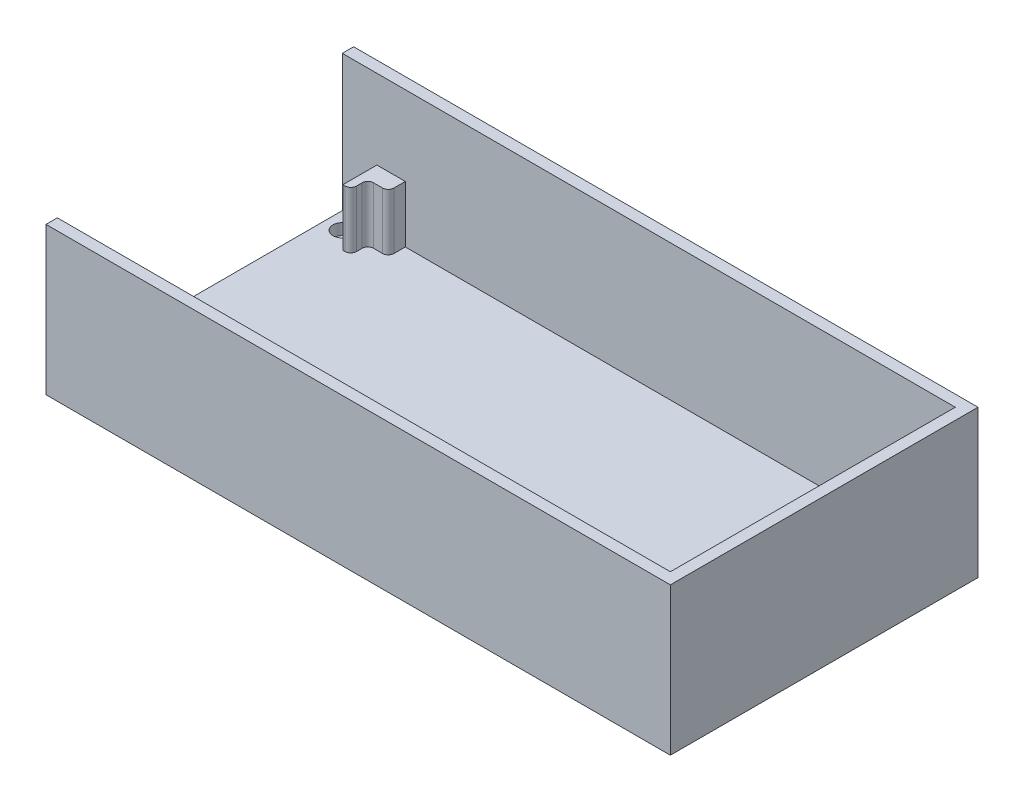
SolidWorks part; units mm, degrees
ref_plane "前视基准面" through (0, 0, 0) normal (0, 0, 1) x (1, 0, 0)
ref_plane "上视基准面" through (0, 0, 0) normal (0, 1, 0) x (1, 0, 0)
ref_plane "右视基准面" through (0, 0, 0) normal (1, 0, 0) x (0, 0, -1)
sketch "草图1" plane through (0, 0, 0) normal (0, 1, 0) x (1, 0, 0)
  line L0 (-56, -27.1) -> (-56, 27.1)
  line L1 (-54, -25.1) -> (54, -25.1)
  line L2 (-54, -25.1) -> (-54, 25.1)
  line L3 (-54, 25.1) -> (54, 25.1)
  line L4 (54, -25.1) -> (54, 25.1)
  line L5 (-54, -25.1) -> (54, 25.1) construction
  line L6 (-54, 25.1) -> (54, -25.1) construction
  line L7 (-56, 27.1) -> (56, 27.1)
  line L8 (56, -27.1) -> (56, 27.1)
  line L9 (-56, -27.1) -> (56, -27.1)
  point P0 (0, 0)
  dimension "D1" = 108
  dimension "D2" = 50.2
  dimension "D3" = 2
extrude "凸台-拉伸1" add sketch "草图1" along normal blind 26
sketch "草图2" plane through (0, 0, 0) normal (0, 1, 0) x (1, 0, 0)
  line L0 (-54, -25.1) -> (54, -25.1) construction
  line L1 (54, -25.1) -> (54, 25.1) construction
  line L2 (-54, 25.1) -> (-54, -25.1) construction
  line L3 (54, 25.1) -> (-54, 25.1) construction
  line L4 (-54, -25.1) -> (54, -25.1)
  line L5 (54, -25.1) -> (54, 25.1)
  line L6 (-54, 25.1) -> (-54, -25.1)
  line L7 (54, 25.1) -> (-54, 25.1)
  line L8 (0, 0) -> (-4.4301, 0) construction
  line L9 (0, 0) -> (0, -5.1784) construction
  circle A0 centre (-51, 22.1) radius 1.65
  circle A4 centre (51, 22.1) radius 1.65
  circle A5 centre (51, -22.1) radius 1.65
  circle A6 centre (-51, -22.1) radius 1.65
  dimension "D1" = 3.3
  dimension "D2" = 3
  dimension "D3" = 3
extrude "凸台-拉伸2" add sketch "草图2" along normal blind 2
sketch "草图4" plane through (-56, 0, 0) normal (-1, 0, 0) x (0, 0, 1)
  line L0 (0, 0) -> (0, 26)
  line L1 (-27.1, 26) -> (27.1, 26) construction
  line L2 (27.1, 26) -> (27.1, 0) construction
  line L3 (-25.1, 24) -> (25.1, 24)
  line L4 (-25.1, 24) -> (-25.1, 2)
  line L5 (-25.1, 2) -> (25.1, 2)
  line L6 (25.1, 24) -> (25.1, 2)
  line L7 (-25.1, 24) -> (25.1, 2) construction
  line L8 (-25.1, 2) -> (25.1, 24) construction
  line L9 (-27.1, 0) -> (27.1, 0) construction
  line L11 (0.1, 21) -> (20.1, 21)
  line L12 (0.1, 21) -> (0.1, 11)
  line L13 (0.1, 11) -> (20.1, 11)
  line L14 (20.1, 21) -> (20.1, 11)
  line L15 (0.1, 21) -> (20.1, 11) construction
  line L16 (0.1, 11) -> (20.1, 21) construction
  circle A0 centre (-16, 6) radius 3.5
  point P5 (0, 13)
  point P14 (10.1, 16)
  dimension "D7" = 4
  dimension "D8" = 7
  dimension "D1" = 2
  dimension "D2" = 2
  dimension "D3" = 20
  dimension "D4" = 10
  dimension "D5" = 5
  dimension "D6" = 5
  dimension "D9" = 16
sketch "草图6" plane through (0, 2, 0) normal (0, 1, 0) x (1, 0, 0)
  line L0 (-47.9, 25.1) -> (-47.9, 19.1)
  line L1 (54, 25.1) -> (-54, 25.1) construction
  line L2 (-47.9, 19.1) -> (-46.5, 19.1)
  line L6 (0, 0) -> (0, 5.3216) construction
  line L8 (46.5, 19.1) -> (46.5, 22.1)
  line L9 (47.9, 19.1) -> (46.5, 19.1)
  line L10 (47.9, 25.1) -> (47.9, 19.1)
  line L11 (-46.5, 22.1) -> (-46.5, 19.1)
  line L12 (0, 0) -> (4.1224, 0) construction
  line L13 (47.9, -25.1) -> (47.9, -19.1)
  line L14 (47.9, -19.1) -> (46.5, -19.1)
  line L15 (46.5, -19.1) -> (46.5, -22.1)
  line L17 (-42.9, -25.1) -> (-47.9, -25.1)
  line L18 (-46.5, -19.1) -> (-46.5, -22.1)
  line L19 (-47.9, -19.1) -> (-46.5, -19.1)
  line L20 (-47.9, -25.1) -> (-47.9, -19.1)
  line L21 (-46.5, 22.1) -> (-42.9, 22.1)
  line L22 (-42.9, 22.1) -> (-42.9, 25.1)
  line L24 (-47.9, 25.1) -> (-42.9, 25.1)
  line L25 (-54, 25.1) -> (-54, -25.1) construction
  line L26 (-46.5, -22.1) -> (-42.9, -22.1)
  line L27 (-42.9, -22.1) -> (-42.9, -25.1)
  line L28 (42.9, -22.1) -> (42.9, -25.1)
  line L29 (46.5, -22.1) -> (42.9, -22.1)
  line L31 (46.5, 22.1) -> (42.9, 22.1)
  line L32 (42.9, 22.1) -> (42.9, 25.1)
  line L33 (47.9, 25.1) -> (42.9, 25.1)
  line L34 (42.9, -25.1) -> (47.9, -25.1)
  point P7 (-42.9, 23.6)
  dimension "D1" = 1.4
  dimension "D2" = 6
  dimension "D3" = 6.1
  dimension "D4" = 3
  dimension "D5" = 5
extrude "凸台-拉伸3" add sketch "草图6" along normal blind 10
sketch "草图9" plane through (-56, 0, 0) normal (-1, 0, 0) x (0, 0, 1)
  line L0 (0.1, 21) -> (0.1, 11) construction
  line L1 (0.1, 21) -> (20.1, 21) construction
  line L2 (20.1, 21) -> (20.1, 11) construction
  line L3 (0.1, 11) -> (20.1, 11) construction
  line L4 (0.1, 21) -> (0.1, 11)
  line L5 (0.1, 21) -> (20.1, 21)
  line L6 (20.1, 21) -> (20.1, 11)
  line L7 (0.1, 11) -> (20.1, 11)
  circle A0 centre (-16, 6) radius 3.5 construction
  circle A1 centre (-16, 6) radius 3.5
extrude "切除-拉伸2" cut sketch "草图9" against normal up to surface (2 mm away) up to face at (-54, 14, 0)
fillet "圆角2" radius 2 5 edges at (-56, 16, 20.1) (-56, 21, 10.1) (-56, 16, 0.1) (-56, 11, 10.1) (-56, 6, -12.5)
sketch "草图10" plane through (-56, 0, 0) normal (-1, 0, 0) x (0, 0, 1)
  line L1 (-27.1, 0) -> (27.1, 0)
  line L2 (-27.1, 0) -> (-27.1, 26)
  line L3 (-27.1, 26) -> (27.1, 26)
  line L4 (27.1, 0) -> (27.1, 26)
extrude "切除-拉伸3" cut sketch "草图10" against normal up to surface (2 mm away) up to face at (-54, 16, 10.1)
fillet "圆角3" radius 1 12 edges at (46.5, 7, -19.1) (46.5, 7, -22.1) (42.9, 7, -22.1) (-46.5, 7, -22.1) (-42.9, 7, -22.1) (-46.5, 7, -19.1) (-42.9, 7, 22.1) (-46.5, 7, 22.1) (-46.5, 7, 19.1) (42.9, 7, 22.1) (46.5, 7, 22.1) (46.5, 7, 19.1)
